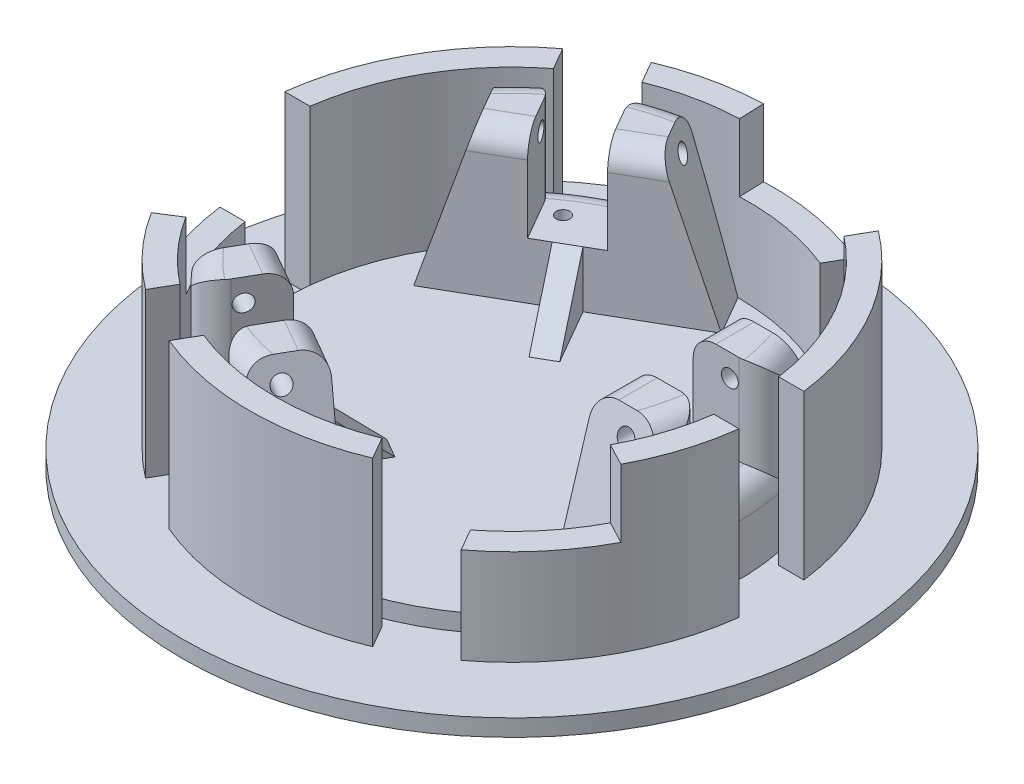
SolidWorks part; units mm, degrees
ref_plane "Front Plane" through (0, 0, 0) normal (0, 0, 1) x (1, 0, 0)
ref_plane "Top Plane" through (0, 0, 0) normal (0, 1, 0) x (1, 0, 0)
ref_plane "Right Plane" through (0, 0, 0) normal (1, 0, 0) x (0, 0, -1)
sketch "Sketch2" plane through (0, 0, 0) normal (0, 0, 1) x (1, 0, 0)
  line L0 (0, 0) -> (15, 0)
  line L1 (15, 0) -> (15, 14.5)
  line L2 (15, 14.5) -> (11, 14.5)
  line L3 (11, 14.5) -> (11, 1.5)
  line L4 (11, 1.5) -> (0, 1.5)
  line L5 (0, 1.5) -> (0, 0)
  dimension "D1" = 15
  dimension "D2" = 14.5
  dimension "D3" = 4
  dimension "D4" = 1.5
extrude "Boss-Extrude1" add sketch "Sketch2" along normal blind 20
ref_plane "Plane2" through (0, 0, 10) normal (0, 0, 1) x (1, 0, 0)
sketch "Sketch9" plane through (0, 1.5, 0) normal (0, 1, 0) x (1, 0, 0)
  line L0 (5.5, -20) -> (0, -12.5)
  line L1 (11, -20) -> (0, -20) construction
  line L2 (0, -20) -> (0, 0) construction
  line L3 (0, -12.5) -> (0, -7.5)
  line L4 (0, -7.5) -> (5.5, 0)
  line L5 (11, 0) -> (0, 0) construction
  line L6 (5.5, 0) -> (0, 0)
  line L7 (0, 0) -> (0, -20)
  line L8 (0, -20) -> (5.5, -20)
  point P14 (0, -10)
  point P15 (0, -10)
  line M3 (11, 0) -> (0, 0)
  line M4 (0, 0) -> (0, -20)
  line M5 (0, -20) -> (11, -20)
  dimension "D3" = 5
extrude "Cut-Extrude6" cut sketch "Sketch9" against normal through all contours L4 M4 M3 | L0 M5 M4 region at (1.8333, 1.5, 17.5) region at (1.8333, 1.5, 2.5)
sketch "Sketch10" plane through (11, 0, 0) normal (-1, 0, 0) x (0, 0, 1)
  line L0 (0, 1.5) -> (0, 14.5)
  line L1 (0, 14.5) -> (20, 14.5)
  line L2 (20, 14.5) -> (20, 1.5)
  line L3 (20, 1.5) -> (16, 14.5)
  line L4 (16, 14.5) -> (4, 14.5)
  line L5 (4, 14.5) -> (0, 1.5)
  line L6 (0, 1.5) -> (0.1757, 1.9576)
  line L7 (20, 14.5) -> (0, 14.5) construction
  line L8 (7.4, 14.5) -> (7.4, 6.5)
  line L9 (7.4, 6.5) -> (12.6, 6.5)
  line L10 (12.6, 6.5) -> (12.6, 14.5)
  point P4 (10, 6.5)
  point P13 (10, 14.5)
  point P14 (10, 14.5)
  line M1 (0, 14.5) -> (0, 1.5)
  line M3 (20, 1.5) -> (20, 14.5)
  line M4 (20, 14.5) -> (0, 14.5)
  dimension "D1" = 6
  dimension "D2" = 5.2
  dimension "D3" = 8
extrude "Cut-Extrude8" cut sketch "Sketch10" against normal through all contours L5 M4 M1 | L9 L10 L4 L8 | L3 M3 M4 region at (11, 10.1667, 18.6667) region at (11, 10.5, 10) region at (11, 10.1667, 1.3333)
sketch "Sketch12" plane through (0, 0, 10) normal (0, 0, 1) x (1, 0, 0)
  line L0 (5.377, 1.5) -> (11, 6.5)
  line L1 (5.5, 1.5) -> (0, 1.5) construction
  line L2 (11, 6.5) -> (11, 1.5)
  line L3 (11, 1.5) -> (5.377, 1.5)
extrude "Boss-Extrude3" add sketch "Sketch12" along normal mid plane 2
sketch "Sketch13" plane through (0, 0, 0) normal (0, 1, 0) x (1, 0, 0)
  line L0 (15, -20) -> (15, 0)
  arc A0 (15, 0) -> (15, -20) centre (-2.4935, -10) cw
  dimension "D1" = 20.15
extrude "Boss-Extrude4" add sketch "Sketch13" along normal up to surface (14.5 mm away) up to face at (13, 14.5, 5.7)
sketch "Sketch14" plane through (15, 0, 0) normal (-1, 0, 0) x (0, 0, 1)
  line L0 (16, 14.5) -> (20, 1.5)
  line L1 (20, 1.5) -> (20, 14.5)
  line L2 (20, 14.5) -> (16, 14.5)
  line L3 (4, 14.5) -> (0, 14.5)
  line L4 (0, 14.5) -> (0, 1.5)
  line L5 (0, 1.5) -> (4, 14.5)
  line L7 (7.4, 14.5) -> (12.6, 14.5)
  line L8 (7.4, 14.5) -> (7.4, 6.5)
  line L9 (7.4, 6.5) -> (12.6, 6.5)
  line L10 (12.6, 14.5) -> (12.6, 6.5)
extrude "Cut-Extrude10" cut sketch "Sketch14" against normal through all
sketch "Sketch15" plane through (0, 6.5, 0) normal (0, 1, 0) x (1, 0, 0)
  line L0 (11, -9) -> (11, 0) construction
  line L1 (17.4881, -7.4) -> (11, -7.4) construction
  circle A0 centre (14, -8.9) radius 0.6
  dimension "D1" = 1.2
  dimension "D2" = 3
  dimension "D3" = 1.5
extrude "Cut-Extrude11" cut sketch "Sketch15" against normal blind 25
fillet "Fillet1" radius 2 7 edges at (17.1888, 14.5, 5.6839) (17.1888, 14.5, 14.3161) (11, 14.5, 14.3) (11, 14.5, 5.7) (17.4881, 10.5, 7.4) (17.4881, 10.5, 12.6) (17.6565, 6.5, 10)
sketch "Sketch11" plane through (0, 0, 7.4) normal (0, 0, 1) x (1, 0, 0)
  line L0 (14.6361, 14.5) -> (13, 14.5) construction
  line L1 (11, 1.5) -> (11, 12.5) construction
  circle A0 centre (14.25, 12.5) radius 0.75
  dimension "D1" = 1.5
  dimension "D2" = 2
  dimension "D3" = 3.25
extrude "Cut-Extrude9" cut sketch "Sketch11" against normal through all both and the other way through all
sketch "Sketch16" plane through (0, 0, 0) normal (0, 1, 0) x (1, 0, 0)
  line L0 (0, -12.5) -> (0, -7.5) construction
  line L33 (-2.4935, 10.15) -> (-2.4935, -30.15) construction
  circle A0 centre (-2.4935, -10) radius 20.15
  circle A2 centre (-2.4935, -10) radius 29.2554
  arc A5 (16.9986, -15.1069) -> (16.9986, -4.8931) centre (-2.4935, -10) ccw construction
  point P7 (0, -10)
  dimension "D1" = 40.3
extrude "Boss-Extrude5" add sketch "Sketch16" against normal blind 1.5
sketch "Sketch22" plane through (0, -1.5, 0) normal (0, -1, 0) x (-1, 0, 0)
  circle A0 centre (2.4935, -10) radius 20.15
  dimension "D1" = 40.3
extrude "Boss-Extrude9" add sketch "Sketch22" against normal up to surface (1.5 mm away) up to face at (14, 0, 9.5)
sketch "Sketch23" plane through (0, 1.5, 0) normal (0, 1, 0) x (1, 0, 0)
  circle A0 centre (-2.4935, -10) radius 20.15
  arc A3 (-19.987, 0) -> (15, -20) centre (-2.4935, -10) ccw construction
  dimension "D1" = 40.3
pattern_circular "CirPattern5" count 3 over 360 about axis through (-2.4935, 0, 10) along (0, 1, 0) of "Boss-Extrude1", "Cut-Extrude6", "Cut-Extrude8", "Boss-Extrude3", "Boss-Extrude4", "Cut-Extrude10", "Cut-Extrude11", "Fillet1", "Cut-Extrude9"
sketch "Sketch24" plane through (0, -1.5, 0) normal (0, -1, 0) x (1, 0, 0)
  circle A0 centre (-2.4935, 10) radius 20.15
  dimension "D1" = 40.3
extrude "Boss-Extrude10" add sketch "Sketch24" against normal up to surface (3 mm away) up to face at (-8.1182, 1.5, 3.507)
sketch "Sketch25" plane through (0, -1.5, 0) normal (0, 1, 0) x (1, 0, 0)
  circle A0 centre (-2.4935, -10) radius 21
  circle A1 centre (-2.4935, -10) radius 23.2191
  dimension "D1" = 42
extrude "Boss-Extrude11" add sketch "Sketch25" along normal up to surface (16 mm away) up to face at (-14.3028, 14.5, -2.5144)
sketch "Sketch26" plane through (0, 14.5, 0) normal (0, 1, 0) x (1, 0, 0)
  line L0 (29.0151, -7.125) -> (29.0151, -12.875)
  line L2 (11, -11) -> (11, -9) construction
  line L3 (11, -10) -> (29.0151, -10) construction
  line L4 (29.0151, -7.125) -> (17.9873, -7.125)
  line L5 (17.9873, -7.125) -> (17.9873, -12.875)
  line L6 (17.9873, -12.875) -> (29.0151, -12.875)
  line L7 (15.7506, -35.8497) -> (10.771, -38.7247)
  line L8 (5.2571, -29.1744) -> (10.771, -38.7247)
  line L9 (10.2367, -26.2994) -> (5.2571, -29.1744)
  line L10 (15.7506, -35.8497) -> (10.2367, -26.2994)
  line L11 (-15.758, -38.7247) -> (-20.7376, -35.8497)
  line L12 (-15.2237, -26.2994) -> (-20.7376, -35.8497)
  line L13 (-10.2441, -29.1744) -> (-15.2237, -26.2994)
  line L14 (-15.758, -38.7247) -> (-10.2441, -29.1744)
  line L15 (-34.0021, -12.875) -> (-34.0021, -7.125)
  line L16 (-22.9743, -7.125) -> (-34.0021, -7.125)
  line L17 (-22.9743, -12.875) -> (-22.9743, -7.125)
  line L18 (-34.0021, -12.875) -> (-22.9743, -12.875)
  line L19 (-20.7376, 15.8497) -> (-15.758, 18.7247)
  line L20 (-10.2441, 9.1744) -> (-15.758, 18.7247)
  line L21 (-15.2237, 6.2994) -> (-10.2441, 9.1744)
  line L22 (-20.7376, 15.8497) -> (-15.2237, 6.2994)
  line L23 (10.771, 18.7247) -> (15.7506, 15.8497)
  line L24 (10.2367, 6.2994) -> (15.7506, 15.8497)
  line L25 (5.2571, 9.1744) -> (10.2367, 6.2994)
  line L26 (10.771, 18.7247) -> (5.2571, 9.1744)
  point P31 (-2.4935, -10)
  dimension "D1" = 5.75
  dimension "D2" = 6
extrude "Cut-Extrude12" cut sketch "Sketch26" against normal up to surface (14.5 mm away) up to face at (-2.4935, 0, 33.2191)
sketch "Sketch27" plane through (0, 14.5, 0) normal (0, 1, 0) x (1, 0, 0)
  line L0 (16.0698, -19.8186) -> (18.0313, -20.8561)
  line L2 (10.3975, -26.5778) -> (11.5165, -28.5161)
  line L3 (20.5469, -12.875) -> (18.3088, -12.875)
  line L4 (10.3975, -26.5778) -> (11.5165, -28.5161)
  arc A2 (10.3975, -26.5778) -> (18.3088, -12.875) centre (-2.4935, -10) ccw
  arc A3 (11.5165, -28.5161) -> (20.5469, -12.875) centre (-2.4935, -10) ccw
  arc A4 (10.3975, -26.5778) -> (16.0698, -19.8186) centre (-2.4935, -10) ccw
  arc A5 (11.5165, -28.5161) -> (18.0313, -20.8561) centre (-2.4935, -10) ccw
  dimension "D1" = 0
extrude "Cut-Extrude13" cut sketch "Sketch27" against normal blind 6
pattern_circular "CirPattern6" count 3 over 360 about axis through (-2.4935, 0, 10) along (0, 1, 0) of "Cut-Extrude13"
